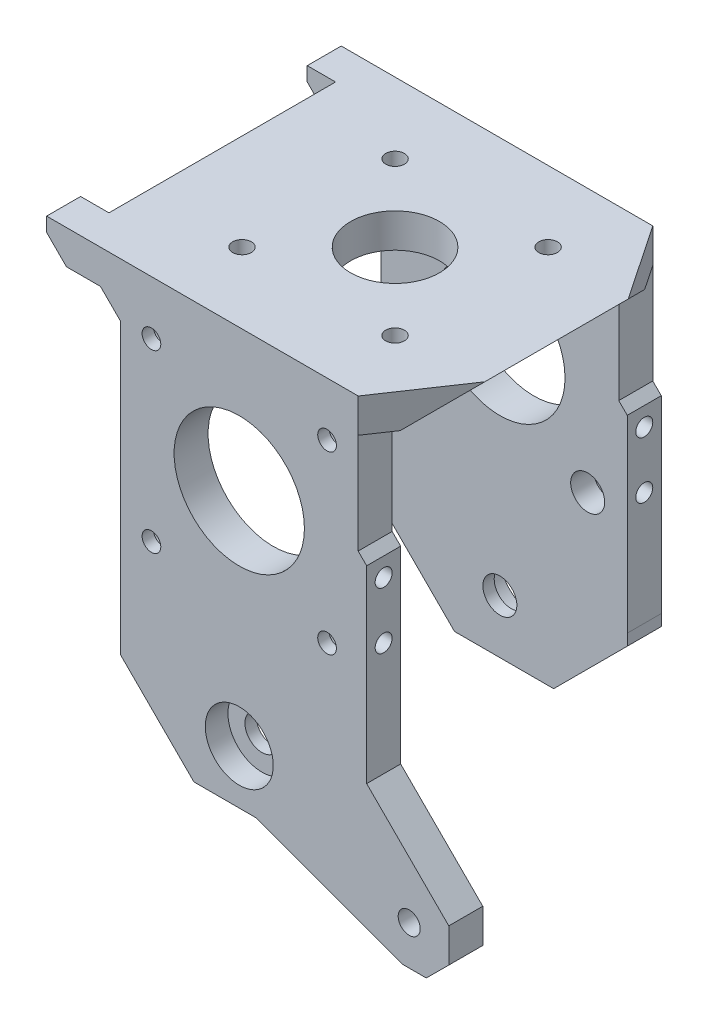
SolidWorks part; units mm, degrees
ref_plane "Front Plane" through (0, 0, 0) normal (0, 0, 1) x (1, 0, 0)
ref_plane "Top Plane" through (0, 0, 0) normal (0, 1, 0) x (1, 0, 0)
ref_plane "Right Plane" through (0, 0, 0) normal (1, 0, 0) x (0, 0, -1)
sketch "Sketch1" plane through (0, 0, 0) normal (0, 0, 1) x (1, 0, 0)
  line L0 (-65.6806, 0) -> (67.5075, 0) construction
  line L1 (0, 51.6446) -> (0, -50.2865) construction
  line L2 (38.003, 38.4634) -> (-25.997, 38.4634)
  line L3 (-25.997, 38.4634) -> (-25.997, 35.9634)
  line L4 (-25.997, 35.9634) -> (-22.4968, 32.4632)
  line L5 (-22.4968, 32.4632) -> (-16.4968, 32.4632)
  line L6 (-16.4968, 32.4632) -> (-12.9966, 28.963)
  line L7 (-12.9966, 28.963) -> (-12.9966, -22.037)
  line L8 (-12.9966, -22.037) -> (0, -35.0336)
  line L9 (0, -35.0336) -> (10.9, -35.0336)
  line L10 (10.9, -35.0336) -> (36.9107, -44.5007)
  line L11 (38.003, 38.4634) -> (31.9926, 32.453)
  line L12 (31.9926, 32.453) -> (28.9926, 32.453)
  line L13 (28.9926, 14.753) -> (30.4917, 13.2539)
  line L14 (30.4917, 13.2539) -> (30.4917, -20.0461)
  line L15 (28.9926, 32.453) -> (28.9926, 14.753)
  line L16 (30.4917, -20.0461) -> (44.9874, -34.5418)
  line L17 (44.9874, -34.5418) -> (44.9874, -40.5418)
  line L18 (36.9107, -44.5007) -> (41.0107, -44.5007)
  line L19 (44.9874, -40.5418) -> (41.0107, -44.5007)
  line L21 (10.9, -35.0336) -> (17.5, -35.0336)
  line L22 (17.5, -35.0336) -> (30.5108, -22.0228)
  line L23 (30.4917, -20.0461) -> (30.5108, -22.0228)
  dimension "D8" = 51
  dimension "D11" = 10.9
  dimension "D1" = 64
  dimension "D2" = 2.5
  dimension "D3" = 4.95
  dimension "D4" = 4.95
  dimension "D5" = 6
  dimension "D6" = 135
  dimension "D7" = 135
  dimension "D9" = 18.38
  dimension "D10" = 135
  dimension "D12" = 27.68
  dimension "D13" = 160
  dimension "D14" = 8.5
  dimension "D15" = 3
  dimension "D16" = 17.7
  dimension "D17" = 45
  dimension "D18" = 33.3
  dimension "D19" = 2.12
  dimension "D20" = 135
  dimension "D21" = 135
  dimension "D22" = 20.5
  dimension "D23" = 17.5
  dimension "D24" = 135
extrude "Boss-Extrude1" add sketch "Sketch1" along normal blind 52 contours L23 L14 L13 L15 L12 L11 L2 L3 L4 L5 L6 L7 L8 L9 L21 L22 region at (8.0846, 4.4295, 0)
extrude "Boss-Extrude3" add sketch "Sketch1<4>" against normal blind 6 from offset 52 contours L16 L23 L22 L21 L10 L18 L19 L17 region at (32.0694, -34.4156, 0)
sketch "Sketch1<4>" plane through (0, 0, 0) normal (0, 0, 1) x (1, 0, 0) same geometry as "Sketch1"
ref_plane "Plane1" through (40.4917, 0, 0) normal (1, 0, 0) x (0, 0, -1)
sketch "Sketch8" plane through (40.4917, 0, 0) normal (1, 0, 0) x (0, 0, -1)
  line L0 (0, -35.0336) -> (-6, -35.0336)
  line L1 (-46, -35.0336) -> (0, -35.0336) construction
  line L2 (-6, -35.0336) -> (-6, 32.453)
  line L3 (-52, 32.453) -> (0, 32.453) construction
  line L4 (-6, 32.453) -> (-46, 32.453)
  line L5 (-46, 32.453) -> (-46, -49.8392)
  line L6 (-46, -49.8392) -> (-6, -35.0336)
extrude "Cut-Extrude5" cut sketch "Sketch8" against normal blind 76 contours L5 L6 L2 L4 region at (40.4917, -5.1137, 26.659)
sketch "Sketch9" plane through (0, 38.4634, 0) normal (0, 1, 0) x (1, 0, 0)
  line L0 (38.003, -26) -> (-25.997, -26) construction
  line L1 (38.003, -52) -> (38.003, 0) construction
  line L2 (-25.997, -52) -> (-25.997, 0) construction
  line L3 (-25.997, -52) -> (-25.997, -40)
  line L4 (-25.997, -40) -> (-20.997, -40)
  line L5 (-20.997, -40) -> (-20.997, -12)
  line L6 (-25.997, -52) -> (29.003, -52)
  line L7 (38.003, -52) -> (-25.997, -52) construction
  line L8 (29.003, -52) -> (37.9511, -38.7361)
  line L9 (37.9511, -38.7361) -> (38.003, -26)
  line L10 (29.003, 0) -> (37.9511, -13.2639)
  line L11 (-25.997, -12) -> (-20.997, -12)
  line L12 (-25.997, -12) -> (-37.6258, -26)
  line L13 (-37.6258, -26) -> (-25.997, -40)
  line L14 (29.003, -52) -> (39.4946, -56.914)
  line L15 (39.4946, -56.914) -> (43.2994, -41.1094)
  line L16 (43.2994, -41.1094) -> (37.9511, -38.7361)
  line L17 (37.9511, -13.2639) -> (46.4671, -6.1903)
  line L18 (46.4671, -6.1903) -> (39.703, 3.8363)
  line L19 (39.703, 3.8363) -> (29.003, 0)
  line L20 (9.503, -26) -> (-4.0027, -12.4943) construction
  circle A0 centre (9.503, -26) radius 7.85
  circle A1 centre (-4.0027, -12.4943) radius 1.65
  circle A2 centre (23.0088, -12.4943) radius 1.65
  circle A3 centre (23.0088, -39.5057) radius 1.65
  circle A4 centre (-4.0027, -39.5057) radius 1.65
  point P18 (-20.997, -26)
  point P37 (9.503, -26)
  line M1 (38.003, 0) -> (-25.997, 0)
  line M2 (-25.997, 0) -> (-25.997, -52)
  line M3 (-25.997, -52) -> (38.003, -52)
  line M4 (38.003, -52) -> (38.003, 0)
  dimension "D1" = 30.5
  dimension "D6" = 15.7
  dimension "D7" = 3.3
  dimension "D2" = 12
  dimension "D3" = 5
  dimension "D4" = 19.1
  dimension "D5" = 45
  dimension "D8" = 4
extrude "Cut-Extrude6" cut sketch "Sketch9" against normal blind 21 contours L10 L17 M4 M1 | L16 L8 M4 M3 | L11 L4 L5 M2 | A0 | A1 | A2 | A3 | A4 region at (-23.497, 38.4634, 26) region at (35.0029, 38.4634, 47.5534) region at (35.0029, 38.4634, 4.4465) region at (9.503, 38.4634, 26) region at (-4.0027, 38.4634, 12.4943) region at (23.0088, 38.4634, 12.4943)
sketch "Sketch14" plane through (0, 0, 52) normal (0, 0, 1) x (1, 0, 0)
  line L0 (-12.9966, 28.963) -> (-12.9966, -22.037) construction
  line L1 (29.003, 38.4634) -> (-25.997, 38.4634) construction
  line L2 (8.0034, 38.4634) -> (8.0034, -36.8131) construction
  line L3 (8.0034, 13.4634) -> (-7.4964, -2.0364) construction
  line L4 (0, -35.0336) -> (10.9, -35.0336) construction
  line L5 (8.0034, -25.5366) -> (38.0028, -37.5355) construction
  circle A0 centre (8.0034, 13.4634) radius 11.5
  circle A1 centre (-7.4964, -2.0364) radius 1.65
  circle A2 centre (-7.4964, 28.9632) radius 1.65
  circle A3 centre (23.5032, 28.9632) radius 1.65
  circle A4 centre (23.5032, -2.0364) radius 1.65
  circle A5 centre (8.0034, -25.5366) radius 3
  circle A6 centre (38.0028, -37.5355) radius 1.95
  point P19 (8.0034, 13.4634)
  dimension "D1" = 23
  dimension "D6" = 3.3
  dimension "D8" = 39
  dimension "D10" = 32.31
  dimension "D12" = 3.9
  dimension "D13" = 6
  dimension "D2" = 21
  dimension "D3" = 25
  dimension "D4" = 45
  dimension "D5" = 21.92
  dimension "D9" = 9.497
  dimension "D11" = 111.8
  dimension "D7" = 4
extrude "Cut-Extrude7" cut sketch "Sketch14" against normal blind 62
sketch "Sketch25" plane through (0, 32.453, 0) normal (0, -1, 0) x (1, 0, 0)
  circle A0 centre (-4.0027, 39.5057) radius 3
  circle A1 centre (23.0088, 39.5057) radius 3
  circle A2 centre (23.0088, 12.4943) radius 3
  circle A3 centre (-4.0027, 12.4943) radius 3
extrude "Cut-Extrude8" cut sketch "Sketch25" against normal blind 3.5
sketch "Sketch26" plane through (0, 0, 0) normal (0, 0, -1) x (-1, 0, 0)
  circle A0 centre (-8.0034, -25.5366) radius 6
extrude "Cut-Extrude9" cut sketch "Sketch26" against normal blind 4
sketch "Sketch27" plane through (0, 0, 52) normal (0, 0, 1) x (1, 0, 0)
  circle A0 centre (8.0034, -25.5366) radius 6
extrude "Cut-Extrude10" cut sketch "Sketch27" against normal blind 4
sketch "Sketch34" plane through (0, 0, 46) normal (0, 0, -1) x (-1, 0, 0)
  circle A0 centre (-23.5032, 28.9632) radius 3
  circle A1 centre (7.4964, 28.9632) radius 3
  circle A2 centre (7.4964, -2.0364) radius 3
  circle A3 centre (-23.5032, -2.0364) radius 3
extrude "Cut-Extrude11" cut sketch "Sketch34" against normal blind 4
sketch "Sketch35" plane through (0, 0, 6) normal (0, 0, 1) x (1, 0, 0)
  circle A0 centre (-7.4964, 28.9632) radius 3
  circle A2 centre (23.5032, -2.0364) radius 3
  circle A3 centre (-7.4964, -2.0364) radius 3
  circle A4 centre (23.5032, 28.9632) radius 3
extrude "Cut-Extrude12" cut sketch "Sketch35" against normal blind 4
sketch "Sketch36" plane through (0, 0, 46) normal (0, 0, -1) x (-1, 0, 0)
  circle A0 centre (-38.0028, -37.5355) radius 4
extrude "Cut-Extrude13" cut sketch "Sketch36" against normal blind 3
sketch "Sketch37" plane through (30.4917, 0, 0) normal (1, 0, 0) x (0, 0, -1)
  line L0 (-3, 13.2539) -> (-3, -5.7877) construction
  line L1 (-6, 13.2539) -> (0, 13.2539) construction
  line L4 (-49, 13.2539) -> (-49, -2.2095) construction
  line L5 (-52, 13.2539) -> (-46, 13.2539) construction
  circle A0 centre (-3, 9.9539) radius 1.5
  circle A2 centre (-3, -0.0461) radius 1.5
  circle A3 centre (-49, 9.9539) radius 1.5
  circle A4 centre (-49, -0.0461) radius 1.5
  dimension "D1" = 3.3
  dimension "D2" = 10
extrude "Cut-Extrude14" cut sketch "Sketch37" against normal blind 5
sketch "Sketch38" plane through (-12.9966, 0, 0) normal (-1, 0, 0) x (0, 0, 1)
  line L0 (49, 28.963) -> (49, -22.037) construction
  line L1 (52, 28.963) -> (46, 28.963) construction
  line L2 (52, -22.037) -> (46, -22.037) construction
  line L3 (3, 28.963) -> (3, -4.3066) construction
  line L4 (6, 28.963) -> (0, 28.963) construction
  circle A0 centre (49, 13.963) radius 1.6
  circle A1 centre (49, 3.963) radius 1.6
  circle A2 centre (3, 13.963) radius 1.6
  circle A3 centre (3, 3.963) radius 1.6
  dimension "D1" = 25
  dimension "D2" = 10
extrude "Cut-Extrude15" cut sketch "Sketch38" against normal blind 4
sketch "Sketch39" plane through (0, 0, 12) normal (0, 0, 1) x (1, 0, 0)
  line L1 (29.003, 38.4634) -> (-25.997, 38.4634) construction
  line L2 (-22.497, 38.4634) -> (-25.997, 38.4634)
  line L3 (-25.997, 38.4634) -> (-28.2765, 32.9704)
  line L4 (-28.2765, 32.9704) -> (-19.1027, 28.6926)
  line L5 (-19.1027, 28.6926) -> (-16.4968, 32.4632)
  line L6 (-16.4968, 32.4632) -> (-20.997, 38.4634)
  line L7 (-20.997, 38.4634) -> (-22.497, 38.4634)
  dimension "D1" = 3.5
extrude "Cut-Extrude16" cut sketch "Sketch39" along normal blind 40 from offset 6 offset against normal yes
